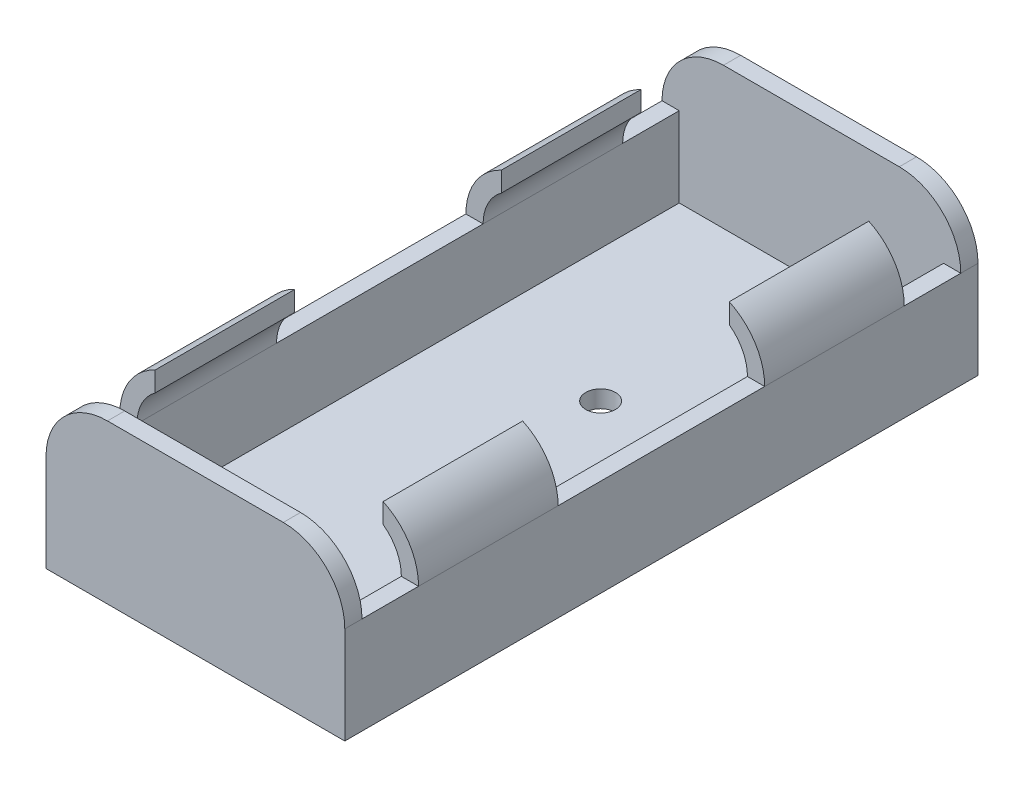
SolidWorks part; units mm, degrees
ref_plane "Front Plane" through (0, 0, 0) normal (0, 0, 1) x (1, 0, 0)
ref_plane "Top Plane" through (0, 0, 0) normal (0, 1, 0) x (1, 0, 0)
ref_plane "Right Plane" through (0, 0, 0) normal (1, 0, 0) x (0, 0, -1)
sketch "Sketch1" plane through (0, 0, 0) normal (0, 0, 1) x (1, 0, 0)
  line L1 (-12.15, 6.45) -> (12.15, 6.45)
  line L2 (-12.15, 6.45) -> (-12.15, -6.45)
  line L3 (-12.15, -6.45) -> (12.15, -6.45)
  line L4 (12.15, 6.45) -> (12.15, -6.45)
  line L5 (-12.15, 6.45) -> (12.15, -6.45) construction
  line L6 (-12.15, -6.45) -> (12.15, 6.45) construction
  point P0 (0, 0)
  dimension "D1" = 24.3
  dimension "D2" = 12.9
extrude "Boss-Extrude1" add sketch "Sketch1" along normal blind 51.5
fillet "Fillet1" radius 5 2 edges at (-12.15, 6.45, 25.75) (12.15, 6.45, 25.75)
shell "Shell1" thickness 1.4 removed face at (0, 6.45, 25.75)
sketch "Sketch2" plane through (0, 6.45, 0) normal (0, 1, 0) x (1, 0, 0)
  line L0 (-10.75, -50.1) -> (10.75, -50.1) construction
  line L1 (-9.2696, -1.4) -> (9.2696, -1.4)
  line L2 (-9.2696, -1.4) -> (-9.2696, -50.1)
  line L3 (-9.2696, -50.1) -> (9.2696, -50.1)
  line L4 (9.2696, -1.4) -> (9.2696, -50.1)
  line L5 (-9.2696, -1.4) -> (9.2696, -50.1) construction
  line L6 (-9.2696, -50.1) -> (9.2696, -1.4) construction
  point P0 (0, -25.75)
extrude "Cut-Extrude1" cut sketch "Sketch2" against normal blind 5
sketch "Sketch3" plane through (0, 6.45, 0) normal (0, 1, 0) x (1, 0, 0)
  line L0 (-12.15, -51.5) -> (-12.15, 0) construction
  line L1 (-12.15, -1.4) -> (12.15, -1.4)
  line L2 (-12.15, -1.4) -> (-12.15, -6)
  line L3 (-12.15, -6) -> (12.15, -6)
  line L4 (12.15, -1.4) -> (12.15, -6)
  line L5 (12.15, 0) -> (12.15, -51.5) construction
  line L6 (7.15, -1.4) -> (-7.15, -1.4) construction
  line L7 (-12.15, -25.75) -> (12.15, -25.75) construction
  line L8 (12.15, -50.1) -> (12.15, -45.5)
  line L9 (-12.15, -45.5) -> (12.15, -45.5)
  line L10 (-12.15, -50.1) -> (-12.15, -45.5)
  line L11 (-12.15, -50.1) -> (12.15, -50.1)
  line L13 (-12.15, -17.35) -> (12.15, -17.35)
  line L14 (-12.15, -17.35) -> (-12.15, -34.15)
  line L15 (-12.15, -34.15) -> (12.15, -34.15)
  line L16 (12.15, -17.35) -> (12.15, -34.15)
  line L17 (-12.15, -17.35) -> (12.15, -34.15) construction
  line L18 (-12.15, -34.15) -> (12.15, -17.35) construction
  point P16 (0, -25.75)
  dimension "D1" = 4.6
  dimension "D2" = 16.8
extrude "Cut-Extrude2" cut sketch "Sketch3" against normal up to vertex (5 mm away) up to point (12.15, 1.45, 0)
sketch "Sketch4" plane through (0, -5.05, 0) normal (0, 1, 0) x (1, 0, 0)
  line L0 (7.15, -51.5) -> (-7.15, -51.5) construction
  line L1 (7.15, 0) -> (-7.15, 0) construction
  circle A0 centre (0, -32.45) radius 1.2065
  circle A1 centre (0, -18.542) radius 1.2065
  dimension "D3" = 2.413
  dimension "D1" = 19.05
  dimension "D2" = 18.542
extrude "Cut-Extrude3" cut sketch "Sketch4" against normal through all
sketch "Sketch5" plane through (0, -5.05, 0) normal (0, 1, 0) x (1, 0, 0)
  line L1 (-1.7321, -6.1215) -> (1.7321, -6.1215)
  line L2 (1.7321, -6.1215) -> (0, -3.1215)
  line L3 (0, -3.1215) -> (-1.7321, -6.1215)
  circle A0 centre (0, -5.1215) radius 1 construction
  dimension "D1" = 3
extrude "Cut-Extrude4" cut sketch "Sketch5" against normal blind 0.2
